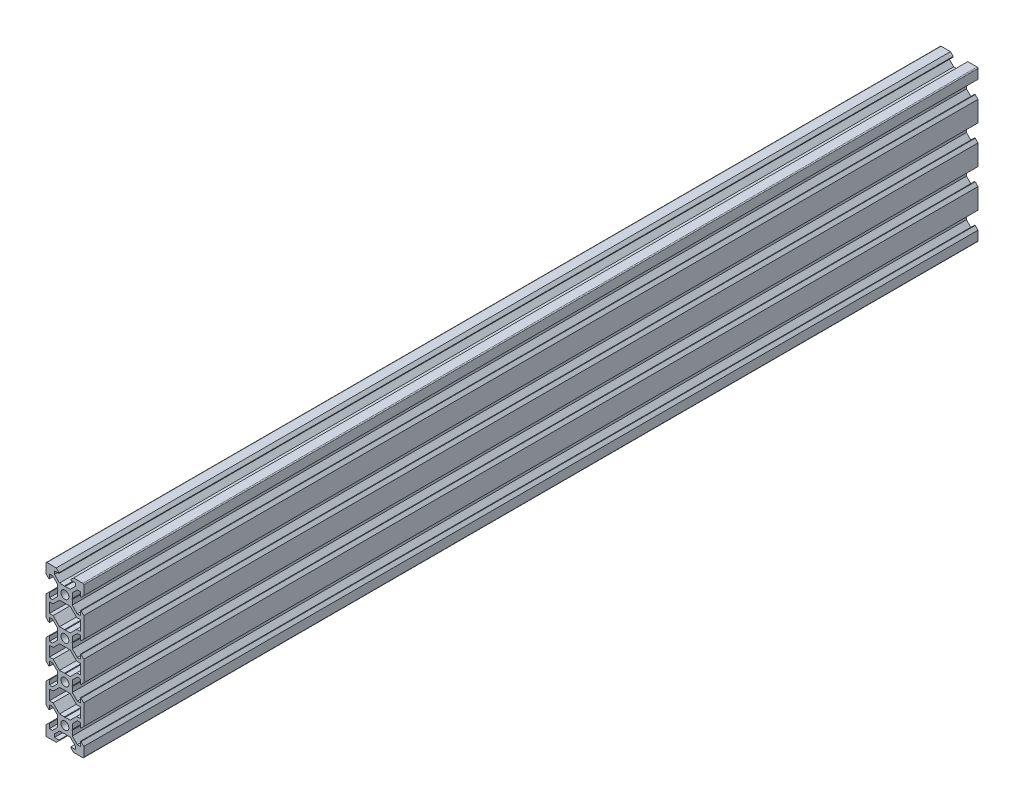
SolidWorks part; units mm, degrees
ref_plane "Plan de face" through (0, 0, 0) normal (0, 0, 1) x (1, 0, 0)
ref_plane "Plan de dessus" through (0, 0, 0) normal (0, 1, 0) x (1, 0, 0)
ref_plane "Plan de droite" through (0, 0, 0) normal (1, 0, 0) x (0, 0, -1)
ref_axis "Axe" through (0, 0, -13.782) along (0, 0, 1)
sketch "Esquisse1" plane through (0, 0, 0) normal (0, 0, 1) x (1, 0, 0)
  line L0 (0, 27.6392) -> (0, -27.6392) construction
  line L1 (-33.6074, 0) -> (33.6074, 0) construction
  line L2 (0, 0) -> (-22.2114, 22.2114) construction
  line L3 (-9.5, 10) -> (-4.58, 10)
  line L4 (-4.58, 10) -> (-3.125, 8.545)
  line L5 (-3.125, 8.545) -> (-3.125, 8.2)
  line L6 (-3.125, 8.2) -> (-5.5, 8.2)
  line L7 (-2.8393, 3.9) -> (-5.5, 6.5607)
  line L8 (-2.8393, 3.9) -> (-0.21, 3.9)
  line L9 (-5.5, 6.5607) -> (-5.5, 8.2)
  line L10 (0, 3.69) -> (0, 2.1)
  line L11 (-3.9, 2.8393) -> (-6.5607, 5.5)
  line L12 (-8.545, 3.125) -> (-8.2, 3.125)
  line L13 (-8.2, 3.125) -> (-8.2, 5.5)
  line L14 (-6.5607, 5.5) -> (-8.2, 5.5)
  line L15 (-10, 4.58) -> (-8.545, 3.125)
  line L16 (-10, 9.5) -> (-10, 4.58)
  line L17 (-0.21, 3.9) -> (0, 3.69)
  line L18 (-3.9, 2.8393) -> (-3.9, 0.21)
  line L19 (-6.2393, -12.7) -> (-8.2, -12.7)
  line L20 (-3.9, 0.21) -> (-3.69, 0)
  line L21 (-0.21, -3.9) -> (0, -3.69)
  line L22 (0, -3.69) -> (0, -2.1)
  line L23 (-6.5607, -5.5) -> (-8.2, -5.5)
  line L24 (-2.8393, -3.9) -> (-0.21, -3.9)
  line L25 (-8.545, -3.125) -> (-8.2, -3.125)
  line L26 (-10, -4.58) -> (-8.545, -3.125)
  line L27 (-8.2, -3.125) -> (-8.2, -5.5)
  line L28 (-2.8393, -3.9) -> (-6.2393, -7.3)
  line L29 (-3.9, -2.8393) -> (-6.5607, -5.5)
  line L30 (-3.9, -2.8393) -> (-3.9, -0.21)
  line L31 (-3.9, -0.21) -> (-3.69, 0)
  line L32 (-6.2393, -7.3) -> (-8.2, -7.3)
  line L33 (-8.2, -7.3) -> (-8.2, -12.7)
  line L34 (-8.2, -10) -> (-10, -10) construction
  line L35 (-10, -15.42) -> (-10, -4.58)
  line L36 (-3.9, -19.79) -> (-3.69, -20)
  line L37 (-3.9, -17.1607) -> (-3.9, -19.79)
  line L38 (-3.9, -17.1607) -> (-6.5607, -14.5)
  line L39 (-2.8393, -16.1) -> (-6.2393, -12.7)
  line L40 (-8.2, -16.875) -> (-8.2, -14.5)
  line L41 (-10, -15.42) -> (-8.545, -16.875)
  line L42 (-8.545, -16.875) -> (-8.2, -16.875)
  line L43 (-2.8393, -16.1) -> (-0.21, -16.1)
  line L44 (-6.5607, -14.5) -> (-8.2, -14.5)
  line L45 (0, -16.31) -> (0, -17.9)
  line L46 (-0.21, -16.1) -> (0, -16.31)
  line L47 (-8.2, -30) -> (-10, -30) construction
  line L48 (-3.69, -20) -> (0, -20) construction
  line L49 (-0.21, -23.9) -> (0, -23.69)
  line L50 (0, -23.69) -> (0, -22.1)
  line L51 (-6.5607, -25.5) -> (-8.2, -25.5)
  line L52 (-2.8393, -23.9) -> (-0.21, -23.9)
  line L53 (-8.545, -23.125) -> (-8.2, -23.125)
  line L54 (-10, -24.58) -> (-8.545, -23.125)
  line L55 (-8.2, -23.125) -> (-8.2, -25.5)
  line L56 (-2.8393, -23.9) -> (-6.2393, -27.3)
  line L57 (-3.9, -22.8393) -> (-6.5607, -25.5)
  line L58 (-3.9, -22.8393) -> (-3.9, -20.21)
  line L59 (-3.9, -20.21) -> (-3.69, -20)
  line L60 (-10, -24.58) -> (-10, -35.42)
  line L61 (-8.2, -32.7) -> (-8.2, -27.3)
  line L62 (-3.69, -40) -> (0, -40) construction
  line L63 (-8.2, -50) -> (-10, -50) construction
  line L64 (0, -60) -> (-22.2114, -82.2114) construction
  line L65 (-33.6074, -60) -> (33.6074, -60) construction
  line L66 (0, -87.6392) -> (0, -32.3608) construction
  line L67 (-6.2393, -32.7) -> (-8.2, -32.7)
  line L68 (-3.9, -39.79) -> (-3.69, -40)
  line L69 (-3.9, -37.1607) -> (-3.9, -39.79)
  line L70 (-3.9, -37.1607) -> (-6.5607, -34.5)
  line L71 (-2.8393, -36.1) -> (-6.2393, -32.7)
  line L72 (-8.2, -36.875) -> (-8.2, -34.5)
  line L73 (-10, -35.42) -> (-8.545, -36.875)
  line L74 (-8.545, -36.875) -> (-8.2, -36.875)
  line L75 (-6.2393, -27.3) -> (-8.2, -27.3)
  line L76 (-2.8393, -36.1) -> (-0.21, -36.1)
  line L77 (-6.5607, -34.5) -> (-8.2, -34.5)
  line L78 (0, -36.31) -> (0, -37.9)
  line L79 (-0.21, -36.1) -> (0, -36.31)
  line L80 (-0.21, -43.9) -> (0, -43.69)
  line L81 (0, -43.69) -> (0, -42.1)
  line L82 (-6.5607, -45.5) -> (-8.2, -45.5)
  line L83 (-2.8393, -43.9) -> (-0.21, -43.9)
  line L84 (-8.545, -43.125) -> (-8.2, -43.125)
  line L85 (-10, -44.58) -> (-8.545, -43.125)
  line L86 (-8.2, -43.125) -> (-8.2, -45.5)
  line L87 (-2.8393, -43.9) -> (-6.2393, -47.3)
  line L88 (-3.9, -42.8393) -> (-6.5607, -45.5)
  line L89 (-3.9, -42.8393) -> (-3.9, -40.21)
  line L90 (-3.9, -40.21) -> (-3.69, -40)
  line L91 (-10, -44.58) -> (-10, -55.42)
  line L92 (-8.2, -52.7) -> (-8.2, -47.3)
  line L93 (-6.2393, -52.7) -> (-8.2, -52.7)
  line L94 (-3.9, -59.79) -> (-3.69, -60)
  line L95 (-3.9, -57.1607) -> (-3.9, -59.79)
  line L96 (-3.9, -57.1607) -> (-6.5607, -54.5)
  line L97 (-2.8393, -56.1) -> (-6.2393, -52.7)
  line L98 (-8.2, -56.875) -> (-8.2, -54.5)
  line L99 (-10, -55.42) -> (-8.545, -56.875)
  line L100 (-8.545, -56.875) -> (-8.2, -56.875)
  line L101 (-2.8393, -56.1) -> (-0.21, -56.1)
  line L102 (-6.5607, -54.5) -> (-8.2, -54.5)
  line L103 (0, -56.31) -> (0, -57.9)
  line L104 (-0.21, -56.1) -> (0, -56.31)
  line L105 (-3.9, -60.21) -> (-3.69, -60)
  line L106 (-6.2393, -47.3) -> (-8.2, -47.3)
  line L107 (-3.9, -62.8393) -> (-3.9, -60.21)
  line L108 (-0.21, -63.9) -> (0, -63.69)
  line L109 (-10, -69.5) -> (-10, -64.58)
  line L110 (-10, -64.58) -> (-8.545, -63.125)
  line L111 (-6.5607, -65.5) -> (-8.2, -65.5)
  line L112 (-8.2, -63.125) -> (-8.2, -65.5)
  line L113 (-8.545, -63.125) -> (-8.2, -63.125)
  line L114 (-3.9, -62.8393) -> (-6.5607, -65.5)
  line L115 (0, -63.69) -> (0, -62.1)
  line L116 (-5.5, -66.5607) -> (-5.5, -68.2)
  line L117 (-2.8393, -63.9) -> (-0.21, -63.9)
  line L118 (-2.8393, -63.9) -> (-5.5, -66.5607)
  line L119 (-3.125, -68.2) -> (-5.5, -68.2)
  line L120 (-3.125, -68.545) -> (-3.125, -68.2)
  line L121 (-4.58, -70) -> (-3.125, -68.545)
  line L122 (-9.5, -70) -> (-4.58, -70)
  arc A0 (0, -2.1) -> (0, 2.1) centre (0, 0) cw
  arc A1 (-9.5, 10) -> (-10, 9.5) centre (-9.5, 9.5) ccw
  arc A2 (0, -42.1) -> (0, -37.9) centre (0, -40) cw
  arc A3 (-9.5, -70) -> (-10, -69.5) centre (-9.5, -69.5) cw
  arc A4 (0, -17.9) -> (0, -22.1) centre (0, -20) ccw
  arc A5 (0, -57.9) -> (0, -62.1) centre (0, -60) ccw
  point P4 (0, 0)
  point P7 (0, 0)
  point P30 (-10, 10)
  point P60 (0, -20)
  point P146 (-10, -70)
  dimension "D5" = 11
  dimension "D2" = 2.1
  dimension "D3" = 6.25
  dimension "D10" = 0.5
  dimension "D4" = 9.16
  dimension "D6" = 1.5
  dimension "D7" = 1.8
  dimension "D8" = 4.3
  dimension "D9" = 20
  dimension "D11" = 0.42
  dimension "D12" = 10
  dimension "D13" = 1.8
extrude "Boss.-Extru.1" add sketch "Esquisse1" along normal blind 473.43
sketch "Esquisse3" plane through (0, 0, 473.43) normal (0, 0, 1) x (1, 0, 0)
  line L0 (0, 0) -> (-9.8536, 9.8536) construction
  line L1 (-8.2, 8.2) -> (-8.2, 6.57)
  line L2 (-8.2, 6.57) -> (-7.54, 6.57)
  line L3 (-7.54, 6.57) -> (-6.57, 7.54)
  line L4 (-8.2, 3.125) -> (-8.2, 5.5) construction
  line L5 (-6.57, 8.2) -> (-6.57, 7.54)
  line L6 (-8.2, 8.2) -> (-6.57, 8.2)
  line L7 (-5.5, 6.5607) -> (-5.5, 8.2) construction
  line L8 (-10, -30) -> (6.918, -30) construction
  line L9 (-10, -24.58) -> (-10, -35.42) construction
  line L10 (-8.2, -68.2) -> (-6.57, -68.2)
  line L11 (-6.57, -68.2) -> (-6.57, -67.54)
  line L12 (-7.54, -66.57) -> (-6.57, -67.54)
  line L13 (-8.2, -66.57) -> (-7.54, -66.57)
  line L14 (-8.2, -68.2) -> (-8.2, -66.57)
  arc A0 (-9.5, 10) -> (-10, 9.5) centre (-9.5, 9.5) ccw construction
  point P13 (-7.055, 7.055)
  point P14 (-6.57, 7.87)
  point P26 (-7.055, -67.055)
  dimension "D1" = 1.07
extrude "Enlèv. mat.-Extru.1" [suppressed] cut sketch "Esquisse3" against normal through all
mirror "Symétrie1" about plane through (0, 3.69, 473.43) normal (-1, 0, 0) of "Enlèv. mat.-Extru.1", "Boss.-Extru.1"
